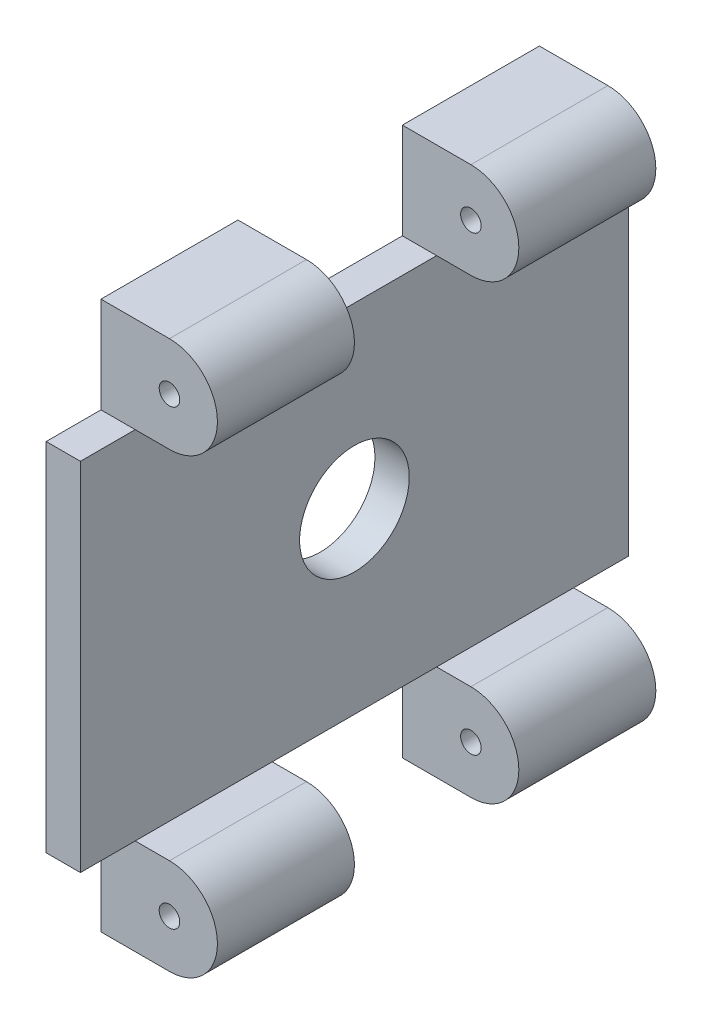
SolidWorks part; units mm, degrees
ref_plane "前视基准面" through (0, 0, 0) normal (0, 0, 1) x (1, 0, 0)
ref_plane "上视基准面" through (0, 0, 0) normal (0, 1, 0) x (1, 0, 0)
ref_plane "右视基准面" through (0, 0, 0) normal (1, 0, 0) x (0, 0, -1)
sketch "草图1" plane through (0, 0, 0) normal (1, 0, 0) x (0, 0, -1)
  line L1 (-40, 40) -> (40, 40)
  line L2 (-40, 40) -> (-40, -40)
  line L3 (-40, -40) -> (40, -40)
  line L4 (40, 40) -> (40, -40)
  line L5 (-40, 40) -> (40, -40) construction
  line L6 (-40, -40) -> (40, 40) construction
  point P0 (0, 0)
  dimension "D1" = 80
  dimension "D2" = 80
extrude "凸台-拉伸1" add sketch "草图1" along normal blind 5
sketch "草图4" plane through (5, 0, 0) normal (1, 0, 0) x (0, 0, -1)
  circle A0 centre (0, 0) radius 8
  dimension "D1" = 16
extrude "切除-拉伸2" cut sketch "草图4" against normal blind 5
sketch "草图6" plane through (0, 0, 40) normal (0, 0, 1) x (1, 0, 0)
  line L3 (5, 40) -> (5, -40) construction
  line L5 (0, 0) -> (5, 0) construction
  line L10 (5, -26) -> (10, -26)
  line L11 (5, 40) -> (10, 40)
  line L12 (5, 40) -> (5, 26)
  line L13 (5, 26) -> (10, 26)
  line L15 (5, -40) -> (5, -26)
  line L16 (5, -40) -> (10, -40)
  arc A0 (10, 40) -> (10, 26) centre (10, 33) cw
  arc A1 (10, -40) -> (10, -26) centre (10, -33) ccw
  dimension "D5" = 14
  dimension "D6" = 5
extrude "凸台-拉伸5" add sketch "草图6" against normal blind 80
sketch "草图7" plane through (0, 0, 0) normal (-1, 0, 0) x (0, 0, 1)
  line L0 (-40, 40) -> (40, 40) construction
  line L1 (-40, 40) -> (-32, 40)
  line L2 (-40, 40) -> (-40, 26)
  line L3 (-40, 26) -> (-32, 26)
  line L4 (-32, 40) -> (-32, 26)
  line L5 (-12, 40) -> (12, 40)
  line L6 (-12, 40) -> (-12, 26)
  line L7 (-12, 26) -> (12, 26)
  line L8 (12, 40) -> (12, 26)
  line L9 (40, 40) -> (40, -40) construction
  line L10 (32, 40) -> (40, 40)
  line L11 (32, 40) -> (32, 26)
  line L12 (32, 26) -> (40, 26)
  line L13 (40, 40) -> (40, 26)
  line L14 (-40, 0) -> (40, 0) construction
  line L15 (-40, -40) -> (-40, 40) construction
  line L16 (40, -40) -> (40, -26)
  line L17 (32, -26) -> (40, -26)
  line L18 (32, -40) -> (32, -26)
  line L19 (32, -40) -> (40, -40)
  line L20 (12, -40) -> (12, -26)
  line L21 (-12, -26) -> (12, -26)
  line L22 (-12, -40) -> (-12, -26)
  line L23 (-12, -40) -> (12, -40)
  line L24 (-32, -40) -> (-32, -26)
  line L25 (-40, -26) -> (-32, -26)
  line L26 (-40, -40) -> (-40, -26)
  line L27 (-40, -40) -> (-32, -40)
  dimension "D1" = 14
  dimension "D2" = 8
  dimension "D3" = 8
  dimension "D4" = 20
  dimension "D5" = 20
extrude "切除-拉伸3" cut sketch "草图7" against normal blind 80
sketch "草图8" plane through (0, 0, 40) normal (0, 0, 1) x (1, 0, 0)
  circle A0 centre (10, 33) radius 1.5
  circle A1 centre (10, -33) radius 1.5
  dimension "D1" = 3
  dimension "D2" = 3
extrude "切除-拉伸4" cut sketch "草图8" against normal blind 80
